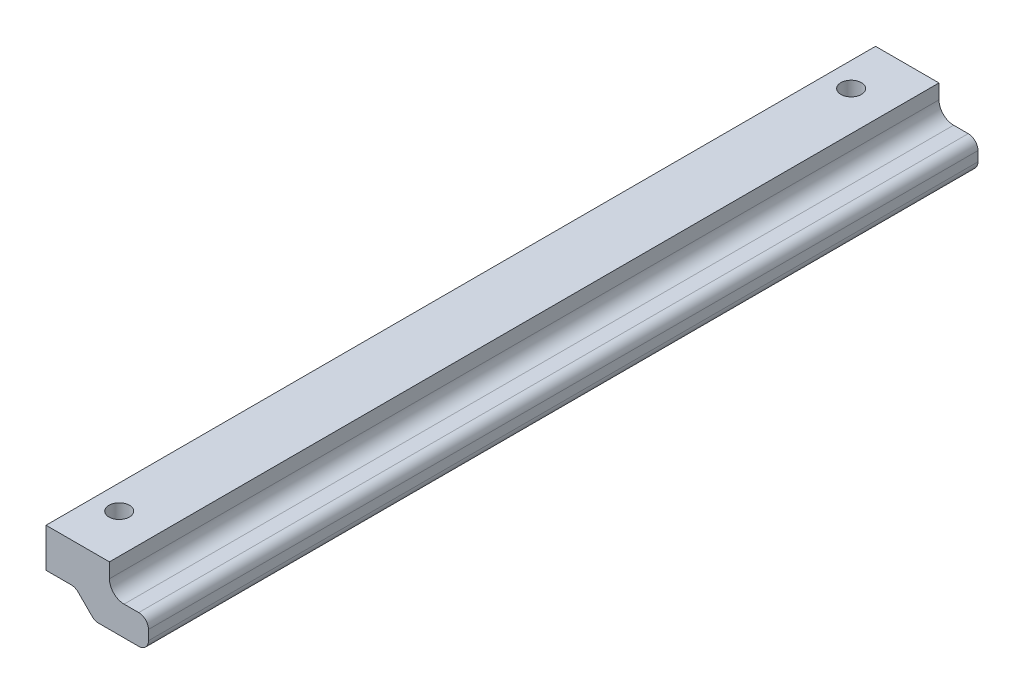
SolidWorks part; units mm, degrees
ref_plane "Front Plane" through (0, 0, 0) normal (0, 0, 1) x (1, 0, 0)
ref_plane "Top Plane" through (0, 0, 0) normal (0, 1, 0) x (1, 0, 0)
ref_plane "Right Plane" through (0, 0, 0) normal (1, 0, 0) x (0, 0, -1)
sketch "Sketch1" plane through (0, 0, 0) normal (0, 0, 1) x (1, 0, 0)
  line L1 (13, -6) -> (13, 0)
  line L2 (55, 0) -> (-55, 0) construction
  line L6 (13, -6) -> (21, -6)
  line L7 (21, -6) -> (21, -12)
  line L8 (0, 0) -> (13, 0)
  line L9 (21, -12) -> (10, -12)
  line L10 (10, -12) -> (6, -8)
  line L11 (6, -8) -> (0, -8)
  line L13 (0, -55) -> (0, 55) construction
  line L14 (0, -8) -> (0, 0)
  dimension "D1" = 6
  dimension "D2" = 6
  dimension "D3" = 8
  dimension "D4" = 10
  dimension "D5" = 8
  dimension "D6" = 45
extrude "Boss-Extrude1" add sketch "Sketch1" against normal blind 170 contours L7 L6 region at (9.8798, -6.062, 0)
fillet "Fillet2" radius 3 1 edges at (13, -6, -85)
sketch "Sketch2" plane through (0, 0, 0) normal (0, 1, 0) x (1, 0, 0)
  line L0 (0, -55) -> (0, 55) construction
  line L1 (-55, 0) -> (55, 0) construction
  circle A0 centre (5, 10) radius 2.1
  circle A1 centre (5, 160) radius 2.1
  dimension "D3" = 4.2
  dimension "D1" = 5
  dimension "D2" = 10
  dimension "D4" = 150
extrude "Cut-Extrude1" cut sketch "Sketch2" against normal up to surface (8 mm away) up to face at (3, -8, -85)
sketch "Sketch3" plane through (0, 0, 0) normal (0, 1, 0) x (1, 0, 0)
  line L0 (0, -55) -> (0, 55) construction
  line L1 (1.55, 11.9919) -> (1.55, 8.0081)
  line L16 (1.55, 8.0081) -> (5, 6.0163)
  line L17 (5, 6.0163) -> (8.45, 8.0081)
  line L18 (8.45, 8.0081) -> (8.45, 11.9919)
  line L19 (8.45, 11.9919) -> (5, 13.9837)
  line L20 (5, 13.9837) -> (1.55, 11.9919)
  line L22 (1.55, 161.9919) -> (1.55, 158.0081)
  line L23 (1.55, 158.0081) -> (5, 156.0163)
  line L24 (5, 156.0163) -> (8.45, 158.0081)
  line L25 (8.45, 158.0081) -> (8.45, 161.9919)
  line L26 (8.45, 161.9919) -> (5, 163.9837)
  line L27 (5, 163.9837) -> (1.55, 161.9919)
  circle A2 centre (5, 10) radius 3.45 construction
  circle A3 centre (5, 160) radius 3.45 construction
  dimension "D1" = 6.9
  dimension "D2" = 6.9
extrude "Cut-Extrude2" cut sketch "Sketch3" along normal blind 8 from surface starting at face at (15.5, -12, -85)
fillet "Fillet3" radius 2 2 edges at (21, -12, -85) (21, -6, -85)
sketch "Sketch4" plane through (0, 0, 0) normal (-1, 0, 0) x (0, 0, 1)
  line L0 (-170, 0) -> (0, 0) construction
  line L1 (-41.4426, 0) -> (-33.4426, 0)
  line L2 (-41.4426, 0) -> (-41.4426, -5)
  line L3 (-41.4426, -5) -> (-33.4426, -5)
  line L4 (-33.4426, 0) -> (-33.4426, -5)
  dimension "D1" = 5
  dimension "D2" = 8
extrude "Cut-Extrude3" [suppressed] cut sketch "Sketch4" against normal up to surface (21 mm away) up to face at (21, -9, -85)
fillet "Fillet4" radius 2 4 edges at (6, -8, -166.7032) (6, -8, -85) (10, -12, -85) (6, -8, -3.2968)
